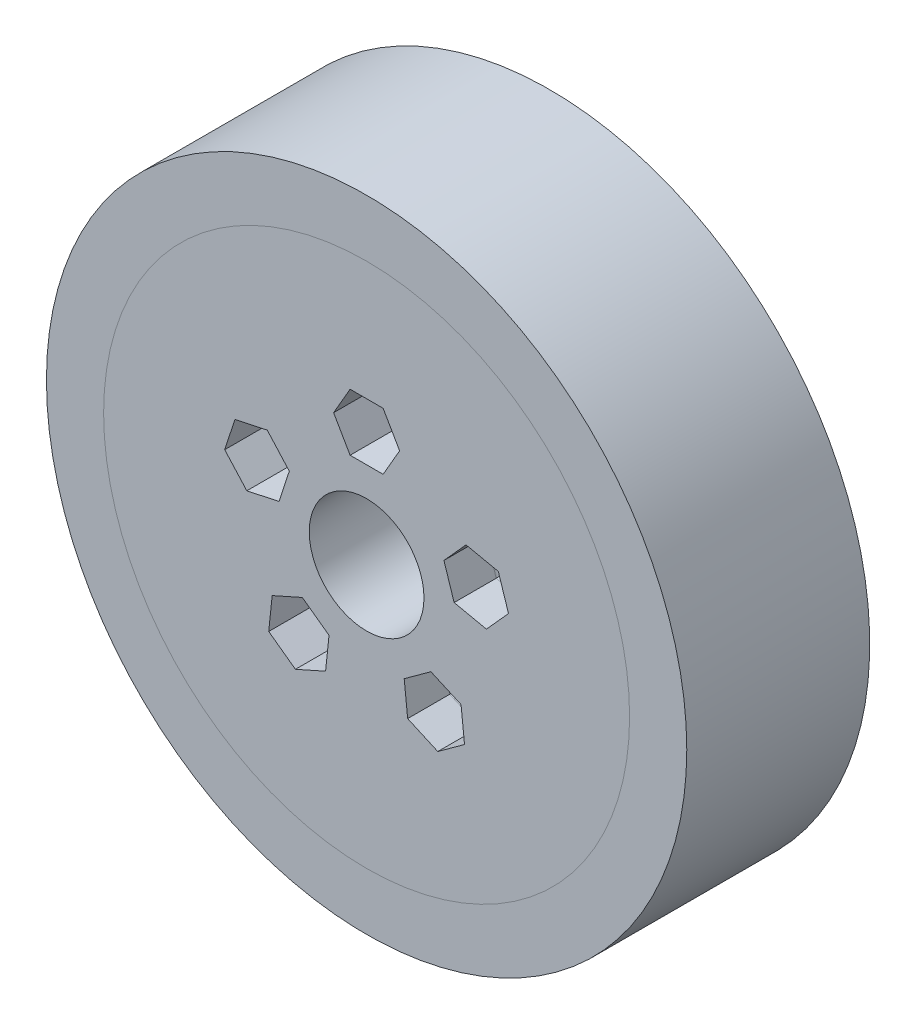
SolidWorks part; units mm, degrees
ref_plane "Front Plane" through (0, 0, 0) normal (0, 0, 1) x (1, 0, 0)
ref_plane "Top Plane" through (0, 0, 0) normal (0, 1, 0) x (1, 0, 0)
ref_plane "Right Plane" through (0, 0, 0) normal (1, 0, 0) x (0, 0, -1)
sketch "Sketch1" plane through (0, 0, 0) normal (0, 0, 1) x (1, 0, 0)
  circle A0 centre (0, 0) radius 44.45 construction
  circle A1 centre (0, 0) radius 36.5125
  circle A2 centre (0, 0) radius 7.9629
  dimension "D1" = 88.9
  dimension "D2" = 15.9258
  dimension "D3" = 7.9375
extrude "Boss-Extrude1" add sketch "Sketch1" along normal blind 25.4
sketch "Sketch3" [suppressed] plane through (0, 0, 0) normal (1, 0, 0) x (0, 0, -1)
  line L0 (-10.3109, 36.5125) -> (-7.3779, 41.5925)
  line L1 (0, 36.5125) -> (-25.4, 36.5125) construction
  line L2 (-7.3779, 41.5925) -> (-4.2029, 41.5925)
  line L3 (-4.2029, 41.5925) -> (-1.27, 36.5125)
  line L4 (0, 0) -> (0, 34.925) construction
  line L5 (0, 0) -> (16.9074, 0) construction
  line L6 (-10.3109, 36.5125) -> (-1.27, 36.5125)
  line L7 (-5.7904, 41.5925) -> (-5.7904, 36.5125) construction
  dimension "D1" = 69.85
  dimension "D2" = 5.08
  dimension "D3" = 30
  dimension "D4" = 3.175
  dimension "D5" = 1.27
revolve "Revolve1" [suppressed] add sketch "Sketch3" angle 360 about L5
sketch "Sketch4" [suppressed] plane through (0, 0, 0) normal (0, 0, 1) x (1, 0, 0)
  line L0 (0, 0) -> (-7.2225, 40.9606) construction
  line L1 (0, 0) -> (7.2225, 40.9606) construction
  line L3 (0, 41.5925) -> (0, 0) construction
  line L4 (7.3339, 41.5925) -> (-7.3339, 41.5925) construction
  line L5 (6.3403, 35.9578) -> (6.9137, 39.2096)
  line L6 (-6.9137, 39.2096) -> (-6.3403, 35.9578)
  circle A0 centre (0, 0) radius 41.5925 construction
  arc A1 (6.9137, 39.2096) -> (-6.9137, 39.2096) centre (0, 0) ccw
  arc A2 (6.3403, 35.9578) -> (-6.3403, 35.9578) centre (0, 0) ccw
  circle A4 centre (0, 0) radius 36.5125 construction
  point P11 (0, 41.5925)
  dimension "D2" = 1.778
  dimension "D1" = 20
extrude "Cut-Extrude2" [suppressed] cut sketch "Sketch4" along normal through all
fillet "Fillet1" [suppressed] radius 1.27
fillet "Fillet2" [suppressed] radius 0.762
pattern_circular "CirPattern1" [suppressed] count 14 over 360 reverse direction yes of bodies 104
split "Split1" [suppressed] bodies to split 105
pattern_linear "LPattern12" [suppressed] count 3 spacing 7.366 of bodies 110
combine bodies "Combine3" [suppressed] bodies to combine 111 114 113 112 110 117
sketch "Sketch2" plane through (0, 0, 0) normal (0, 0, 1) x (1, 0, 0)
  circle A0 centre (0, 0) radius 25.4
  circle A2 centre (0, 0) radius 7.9629 construction
  circle A3 centre (0, 0) radius 7.9629
  dimension "D1" = 50.8
extrude "Boss-Extrude3" add sketch "Sketch2" against normal blind 2.54
sketch "Sketch7" plane through (0, 0, 0) normal (0, 0, -1) x (-1, 0, 0)
  circle A0 centre (0, 0) radius 36.5125 construction
  circle A1 centre (0, 0) radius 44.45 construction
  circle A2 centre (0, 0) radius 36.5125
  circle A3 centre (0, 0) radius 44.45
extrude "Boss-Extrude2" add sketch "Sketch7" against normal up to surface (25.4 mm away) separate body up to face at (36.5125, 0, 25.4)
chamfer "Chamfer1" distance 1.27 angle 45 1 edges at (25.4, 0, -2.54)
sketch "Sketch8" plane through (0, 0, -2.54) normal (0, 0, -1) x (-1, 0, 0)
  line L54 (-3.1722, 20.1603) -> (-3.1669, 20.1266)
  line L55 (-1.56, 20.3144) -> (-1.5626, 20.3484)
  line L56 (1.5626, 20.3484) -> (1.56, 20.3144)
  line L57 (3.1669, 20.1266) -> (3.1722, 20.1603)
  line L58 (6.2131, 19.4395) -> (6.2028, 19.4071)
  line L59 (7.723, 18.8538) -> (7.7359, 18.8853)
  line L60 (10.5287, 17.4827) -> (10.5112, 17.4535)
  line L61 (11.8628, 16.5645) -> (11.8827, 16.5922)
  line L62 (14.2767, 14.5833) -> (14.2529, 14.559)
  line L63 (15.3631, 13.3822) -> (15.3888, 13.4046)
  line L64 (17.255, 10.8978) -> (17.2262, 10.8796)
  line L65 (18.0351, 9.4785) -> (18.0653, 9.4944)
  line L66 (19.3031, 6.6248) -> (19.2709, 6.6137)
  line L67 (19.7349, 5.0639) -> (19.7679, 5.0723)
  line L68 (20.3106, 1.9946) -> (20.2767, 1.9913)
  line L69 (20.3708, 0.3762) -> (20.4048, 0.3768)
  line L70 (20.2231, -2.7431) -> (20.1893, -2.7385)
  line L71 (19.9084, -4.3318) -> (19.9417, -4.339)
  line L72 (19.0454, -7.3329) -> (19.0136, -7.3207)
  line L73 (18.3728, -8.8062) -> (18.4035, -8.8209)
  line L74 (16.8409, -11.5274) -> (16.8128, -11.5082)
  line L75 (15.8467, -12.8059) -> (15.8732, -12.8273)
  line L76 (13.7286, -15.1005) -> (13.7056, -15.0753)
  line L77 (12.4663, -16.1152) -> (12.4872, -16.1422)
  line L78 (9.8761, -17.8595) -> (9.8596, -17.8297)
  line L79 (8.4139, -18.5558) -> (8.4279, -18.5868)
  line L80 (5.4912, -19.6557) -> (5.482, -19.6229)
  line L81 (3.9078, -19.996) -> (3.9143, -20.0294)
  line L82 (0.8103, -20.3922) -> (0.8089, -20.3582)
  line L83 (-0.8089, -20.3582) -> (-0.8103, -20.3922)
  line L84 (-3.9143, -20.0294) -> (-3.9078, -19.996)
  line L85 (-5.482, -19.6229) -> (-5.4912, -19.6557)
  line L86 (-8.4279, -18.5868) -> (-8.4139, -18.5558)
  line L87 (-9.8596, -17.8297) -> (-9.8761, -17.8595)
  line L88 (-12.4872, -16.1422) -> (-12.4663, -16.1152)
  line L89 (-13.7056, -15.0753) -> (-13.7286, -15.1005)
  line L90 (-15.8732, -12.8273) -> (-15.8467, -12.8059)
  line L91 (-16.8128, -11.5082) -> (-16.8409, -11.5274)
  line L92 (-18.4035, -8.8209) -> (-18.3728, -8.8062)
  line L93 (-19.0136, -7.3207) -> (-19.0454, -7.3329)
  line L94 (-19.9417, -4.339) -> (-19.9084, -4.3318)
  line L95 (-20.1893, -2.7385) -> (-20.2231, -2.7431)
  line L96 (-20.4048, 0.3768) -> (-20.3708, 0.3762)
  line L97 (-20.2767, 1.9913) -> (-20.3106, 1.9946)
  line L98 (-19.7679, 5.0723) -> (-19.7349, 5.0639)
  line L99 (-19.2709, 6.6137) -> (-19.3031, 6.6248)
  line L100 (-18.0653, 9.4944) -> (-18.0351, 9.4785)
  line L101 (-17.2262, 10.8796) -> (-17.255, 10.8978)
  line L102 (-15.3888, 13.4046) -> (-15.3631, 13.3822)
  line L103 (-14.2529, 14.559) -> (-14.2767, 14.5833)
  line L104 (-11.8827, 16.5922) -> (-11.8628, 16.5645)
  line L105 (-10.5112, 17.4535) -> (-10.5287, 17.4827)
  line L106 (-7.7359, 18.8853) -> (-7.723, 18.8538)
  line L107 (-6.2028, 19.4071) -> (-6.2131, 19.4395)
  line L108 (-3.1722, 20.1603) -> (-3.1669, 20.1266)
  line L109 (-1.56, 20.3144) -> (-1.5626, 20.3484)
  line L110 (1.5626, 20.3484) -> (1.56, 20.3144)
  line L111 (3.1669, 20.1266) -> (3.1722, 20.1603)
  line L112 (6.2131, 19.4395) -> (6.2028, 19.4071)
  line L113 (7.723, 18.8538) -> (7.7359, 18.8853)
  line L114 (10.5287, 17.4827) -> (10.5112, 17.4535)
  line L115 (11.8628, 16.5645) -> (11.8827, 16.5922)
  line L116 (14.2767, 14.5833) -> (14.2529, 14.559)
  line L117 (15.3631, 13.3822) -> (15.3888, 13.4046)
  line L118 (17.255, 10.8978) -> (17.2262, 10.8796)
  line L119 (18.0351, 9.4785) -> (18.0653, 9.4944)
  line L120 (19.3031, 6.6248) -> (19.2709, 6.6137)
  line L121 (19.7349, 5.0639) -> (19.7679, 5.0723)
  line L122 (20.3106, 1.9946) -> (20.2767, 1.9913)
  line L123 (20.3708, 0.3762) -> (20.4048, 0.3768)
  line L124 (20.2231, -2.7431) -> (20.1893, -2.7385)
  line L125 (19.9084, -4.3318) -> (19.9417, -4.339)
  line L126 (19.0454, -7.3329) -> (19.0136, -7.3207)
  line L127 (18.3728, -8.8062) -> (18.4035, -8.8209)
  line L128 (16.8409, -11.5274) -> (16.8128, -11.5082)
  line L129 (15.8467, -12.8059) -> (15.8732, -12.8273)
  line L130 (13.7286, -15.1005) -> (13.7056, -15.0753)
  line L131 (12.4663, -16.1152) -> (12.4872, -16.1422)
  line L132 (9.8761, -17.8595) -> (9.8596, -17.8297)
  line L133 (8.4139, -18.5558) -> (8.4279, -18.5868)
  line L134 (5.4912, -19.6557) -> (5.482, -19.6229)
  line L135 (3.9078, -19.996) -> (3.9143, -20.0294)
  line L136 (0.8103, -20.3922) -> (0.8089, -20.3582)
  line L137 (-0.8089, -20.3582) -> (-0.8103, -20.3922)
  line L138 (-3.9143, -20.0294) -> (-3.9078, -19.996)
  line L139 (-5.482, -19.6229) -> (-5.4912, -19.6557)
  line L140 (-8.4279, -18.5868) -> (-8.4139, -18.5558)
  line L141 (-9.8596, -17.8297) -> (-9.8761, -17.8595)
  line L142 (-12.4872, -16.1422) -> (-12.4663, -16.1152)
  line L143 (-13.7056, -15.0753) -> (-13.7286, -15.1005)
  line L144 (-15.8732, -12.8273) -> (-15.8467, -12.8059)
  line L145 (-16.8128, -11.5082) -> (-16.8409, -11.5274)
  line L146 (-18.4035, -8.8209) -> (-18.3728, -8.8062)
  line L147 (-19.0136, -7.3207) -> (-19.0454, -7.3329)
  line L148 (-19.9417, -4.339) -> (-19.9084, -4.3318)
  line L149 (-20.1893, -2.7385) -> (-20.2231, -2.7431)
  line L150 (-20.4048, 0.3768) -> (-20.3708, 0.3762)
  line L151 (-20.2767, 1.9913) -> (-20.3106, 1.9946)
  line L152 (-19.7679, 5.0723) -> (-19.7349, 5.0639)
  line L153 (-19.2709, 6.6137) -> (-19.3031, 6.6248)
  line L154 (-18.0653, 9.4944) -> (-18.0351, 9.4785)
  line L155 (-17.2262, 10.8796) -> (-17.255, 10.8978)
  line L156 (-15.3888, 13.4046) -> (-15.3631, 13.3822)
  line L157 (-14.2529, 14.559) -> (-14.2767, 14.5833)
  line L158 (-11.8827, 16.5922) -> (-11.8628, 16.5645)
  line L159 (-10.5112, 17.4535) -> (-10.5287, 17.4827)
  line L160 (-7.7359, 18.8853) -> (-7.723, 18.8538)
  line L161 (-6.2028, 19.4071) -> (-6.2131, 19.4395)
  arc A108 (-2.7438, 20.7336) -> (-3.1722, 20.1603) centre (-2.6782, 20.238) ccw
  arc A109 (-2.1116, 20.8075) -> (-2.7438, 20.7336) centre (0, 0) ccw
  arc A110 (-1.5626, 20.3484) -> (-2.1116, 20.8075) centre (-2.0611, 20.3101) ccw
  arc A111 (-1.56, 20.3144) -> (1.56, 20.3144) centre (0, 20.3144) ccw
  arc A112 (2.1116, 20.8075) -> (1.5626, 20.3484) centre (2.0611, 20.3101) ccw
  arc A113 (2.7438, 20.7336) -> (2.1116, 20.8075) centre (0, 0) ccw
  arc A114 (3.1722, 20.1603) -> (2.7438, 20.7336) centre (2.6782, 20.238) ccw
  arc A115 (3.1669, 20.1266) -> (6.2028, 19.4071) centre (4.6848, 19.7668) ccw
  arc A116 (6.8533, 19.7597) -> (6.2131, 19.4395) centre (6.6894, 19.2873) ccw
  arc A117 (7.4514, 19.542) -> (6.8533, 19.7597) centre (0, 0) ccw
  arc A118 (7.7359, 18.8853) -> (7.4514, 19.542) centre (7.2733, 19.0748) ccw
  arc A119 (7.723, 18.8538) -> (10.5112, 17.4535) centre (9.1171, 18.1536) ccw
  arc A120 (11.2254, 17.6466) -> (10.5287, 17.4827) centre (10.9571, 17.2247) ccw
  arc A121 (11.7572, 17.2968) -> (11.2254, 17.6466) centre (0, 0) ccw
  arc A122 (11.8827, 16.5922) -> (11.7572, 17.2968) centre (11.4762, 16.8833) ccw
  arc A123 (11.8628, 16.5645) -> (14.2529, 14.559) centre (13.0579, 15.5617) ccw
  arc A124 (14.9924, 14.5822) -> (14.2767, 14.5833) centre (14.634, 14.2336) ccw
  arc A125 (15.4292, 14.1192) -> (14.9924, 14.5822) centre (0, 0) ccw
  arc A126 (15.3888, 13.4046) -> (15.4292, 14.1192) centre (15.0604, 13.7816) ccw
  arc A127 (15.3631, 13.3822) -> (17.2262, 10.8796) centre (16.2947, 12.1309) ccw
  arc A128 (17.9512, 10.7316) -> (17.255, 10.8978) centre (17.522, 10.4751) ccw
  arc A129 (18.2695, 10.1804) -> (17.9512, 10.7316) centre (0, 0) ccw
  arc A130 (18.0653, 9.4944) -> (18.2695, 10.1804) centre (17.8327, 9.937) ccw
  arc A131 (18.0351, 9.4785) -> (19.2709, 6.6137) centre (18.653, 8.0461) ccw
  arc A132 (19.9422, 6.3025) -> (19.3031, 6.6248) centre (19.4654, 6.1518) ccw
  arc A133 (20.1248, 5.6927) -> (19.9422, 6.3025) centre (0, 0) ccw
  arc A134 (19.7679, 5.0723) -> (20.1248, 5.6927) centre (19.6436, 5.5566) ccw
  arc A135 (19.7349, 5.0639) -> (20.2767, 1.9913) centre (20.0058, 3.5276) ccw
  arc A136 (20.8581, 1.5336) -> (20.3106, 1.9946) centre (20.3595, 1.497) ccw
  arc A137 (20.8951, 0.8982) -> (20.8581, 1.5336) centre (0, 0) ccw
  arc A138 (20.4048, 0.3768) -> (20.8951, 0.8982) centre (20.3956, 0.8767) ccw
  arc A139 (20.3708, 0.3762) -> (20.1893, -2.7385) centre (20.28, -1.1812) ccw
  arc A140 (20.6496, -3.3179) -> (20.2231, -2.7431) centre (20.1559, -3.2386) ccw
  arc A141 (20.539, -3.9448) -> (20.6496, -3.3179) centre (0, 0) ccw
  arc A142 (19.9417, -4.339) -> (20.539, -3.9448) centre (20.048, -3.8505) ccw
  arc A143 (19.9084, -4.3318) -> (19.0136, -7.3207) centre (19.461, -5.8262) ccw
  arc A144 (19.3278, -7.9906) -> (19.0454, -7.3329) centre (18.8657, -7.7996) ccw
  arc A145 (19.0757, -8.5751) -> (19.3278, -7.9906) centre (0, 0) ccw
  arc A146 (18.4035, -8.8209) -> (19.0757, -8.5751) centre (18.6196, -8.37) ccw
  arc A147 (18.3728, -8.8062) -> (16.8128, -11.5082) centre (17.5928, -10.1572) ccw
  arc A148 (16.9641, -12.2325) -> (16.8409, -11.5274) centre (16.5585, -11.94) ccw
  arc A149 (16.5839, -12.7431) -> (16.9641, -12.2325) centre (0, 0) ccw
  arc A150 (15.8732, -12.8273) -> (16.5839, -12.7431) centre (16.1875, -12.4384) ccw
  arc A151 (15.8467, -12.8059) -> (13.7056, -15.0753) centre (14.7762, -13.9406) ccw
  arc A152 (13.6858, -15.8149) -> (13.7286, -15.1005) centre (13.3586, -15.4369) ccw
  arc A153 (13.1982, -16.2241) -> (13.6858, -15.8149) centre (0, 0) ccw
  arc A154 (12.4872, -16.1422) -> (13.1982, -16.2241) centre (12.8826, -15.8362) ccw
  arc A155 (12.4663, -16.1152) -> (9.8596, -17.8297) centre (11.163, -16.9724) ccw
  arc A156 (9.6697, -18.5448) -> (9.8761, -17.8595) centre (9.4385, -18.1015) ccw
  arc A157 (9.1009, -18.8305) -> (9.6697, -18.5448) centre (0, 0) ccw
  arc A158 (8.4279, -18.5868) -> (9.1009, -18.8305) centre (8.8833, -18.3803) ccw
  arc A159 (8.4139, -18.5558) -> (5.482, -19.6229) centre (6.9479, -19.0893) ccw
  arc A160 (5.1323, -20.2749) -> (5.4912, -19.6557) centre (5.0096, -19.7902) ccw
  arc A161 (4.513, -20.4217) -> (5.1323, -20.2749) centre (0, 0) ccw
  arc A162 (3.9143, -20.0294) -> (4.513, -20.4217) centre (4.4051, -19.9335) ccw
  arc A163 (3.9078, -19.996) -> (0.8089, -20.3582) centre (2.3584, -20.1771) ccw
  arc A164 (0.3183, -20.912) -> (0.8103, -20.3922) centre (0.3107, -20.4121) ccw
  arc A165 (-0.3183, -20.912) -> (0.3183, -20.912) centre (0, 0) ccw
  arc A166 (-0.8103, -20.3922) -> (-0.3183, -20.912) centre (-0.3107, -20.4121) ccw
  arc A167 (-0.8089, -20.3582) -> (-3.9078, -19.996) centre (-2.3584, -20.1771) ccw
  arc A168 (-4.513, -20.4217) -> (-3.9143, -20.0294) centre (-4.4051, -19.9335) ccw
  arc A169 (-5.1323, -20.2749) -> (-4.513, -20.4217) centre (0, 0) ccw
  arc A170 (-5.4912, -19.6557) -> (-5.1323, -20.2749) centre (-5.0096, -19.7902) ccw
  arc A171 (-5.482, -19.6229) -> (-8.4139, -18.5558) centre (-6.9479, -19.0893) ccw
  arc A172 (-9.1009, -18.8305) -> (-8.4279, -18.5868) centre (-8.8833, -18.3803) ccw
  arc A173 (-9.6697, -18.5448) -> (-9.1009, -18.8305) centre (0, 0) ccw
  arc A174 (-9.8761, -17.8595) -> (-9.6697, -18.5448) centre (-9.4385, -18.1015) ccw
  arc A175 (-9.8596, -17.8297) -> (-12.4663, -16.1152) centre (-11.163, -16.9724) ccw
  arc A176 (-13.1982, -16.2241) -> (-12.4872, -16.1422) centre (-12.8826, -15.8362) ccw
  arc A177 (-13.6858, -15.8149) -> (-13.1982, -16.2241) centre (0, 0) ccw
  arc A178 (-13.7286, -15.1005) -> (-13.6858, -15.8149) centre (-13.3586, -15.4369) ccw
  arc A179 (-13.7056, -15.0753) -> (-15.8467, -12.8059) centre (-14.7762, -13.9406) ccw
  arc A180 (-16.5839, -12.7431) -> (-15.8732, -12.8273) centre (-16.1875, -12.4384) ccw
  arc A181 (-16.9641, -12.2325) -> (-16.5839, -12.7431) centre (0, 0) ccw
  arc A182 (-16.8409, -11.5274) -> (-16.9641, -12.2325) centre (-16.5585, -11.94) ccw
  arc A183 (-16.8128, -11.5082) -> (-18.3728, -8.8062) centre (-17.5928, -10.1572) ccw
  arc A184 (-19.0757, -8.5751) -> (-18.4035, -8.8209) centre (-18.6196, -8.37) ccw
  arc A185 (-19.3278, -7.9906) -> (-19.0757, -8.5751) centre (0, 0) ccw
  arc A186 (-19.0454, -7.3329) -> (-19.3278, -7.9906) centre (-18.8657, -7.7996) ccw
  arc A187 (-19.0136, -7.3207) -> (-19.9084, -4.3318) centre (-19.461, -5.8262) ccw
  arc A188 (-20.539, -3.9448) -> (-19.9417, -4.339) centre (-20.048, -3.8505) ccw
  arc A189 (-20.6496, -3.3179) -> (-20.539, -3.9448) centre (0, 0) ccw
  arc A190 (-20.2231, -2.7431) -> (-20.6496, -3.3179) centre (-20.1559, -3.2386) ccw
  arc A191 (-20.1893, -2.7385) -> (-20.3708, 0.3762) centre (-20.28, -1.1812) ccw
  arc A192 (-20.8951, 0.8982) -> (-20.4048, 0.3768) centre (-20.3956, 0.8767) ccw
  arc A193 (-20.8581, 1.5336) -> (-20.8951, 0.8982) centre (0, 0) ccw
  arc A194 (-20.3106, 1.9946) -> (-20.8581, 1.5336) centre (-20.3595, 1.497) ccw
  arc A195 (-20.2767, 1.9913) -> (-19.7349, 5.0639) centre (-20.0058, 3.5276) ccw
  arc A196 (-20.1248, 5.6927) -> (-19.7679, 5.0723) centre (-19.6436, 5.5566) ccw
  arc A197 (-19.9422, 6.3025) -> (-20.1248, 5.6927) centre (0, 0) ccw
  arc A198 (-19.3031, 6.6248) -> (-19.9422, 6.3025) centre (-19.4654, 6.1518) ccw
  arc A199 (-19.2709, 6.6137) -> (-18.0351, 9.4785) centre (-18.653, 8.0461) ccw
  arc A200 (-18.2695, 10.1804) -> (-18.0653, 9.4944) centre (-17.8327, 9.937) ccw
  arc A201 (-17.9512, 10.7316) -> (-18.2695, 10.1804) centre (0, 0) ccw
  arc A202 (-17.255, 10.8978) -> (-17.9512, 10.7316) centre (-17.522, 10.4751) ccw
  arc A203 (-17.2262, 10.8796) -> (-15.3631, 13.3822) centre (-16.2947, 12.1309) ccw
  arc A204 (-15.4292, 14.1192) -> (-15.3888, 13.4046) centre (-15.0604, 13.7816) ccw
  arc A205 (-14.9924, 14.5822) -> (-15.4292, 14.1192) centre (0, 0) ccw
  arc A206 (-14.2767, 14.5833) -> (-14.9924, 14.5822) centre (-14.634, 14.2336) ccw
  arc A207 (-14.2529, 14.559) -> (-11.8628, 16.5645) centre (-13.0579, 15.5617) ccw
  arc A208 (-11.7572, 17.2968) -> (-11.8827, 16.5922) centre (-11.4762, 16.8833) ccw
  arc A209 (-11.2254, 17.6466) -> (-11.7572, 17.2968) centre (0, 0) ccw
  arc A210 (-10.5287, 17.4827) -> (-11.2254, 17.6466) centre (-10.9571, 17.2247) ccw
  arc A211 (-10.5112, 17.4535) -> (-7.723, 18.8538) centre (-9.1171, 18.1536) ccw
  arc A212 (-7.4514, 19.542) -> (-7.7359, 18.8853) centre (-7.2733, 19.0748) ccw
  arc A213 (-6.8533, 19.7597) -> (-7.4514, 19.542) centre (0, 0) ccw
  arc A214 (-6.2131, 19.4395) -> (-6.8533, 19.7597) centre (-6.6894, 19.2873) ccw
  arc A215 (-6.2028, 19.4071) -> (-3.1669, 20.1266) centre (-4.6848, 19.7668) ccw
  arc A216 (-2.7438, 20.7336) -> (-3.1722, 20.1603) centre (-2.6782, 20.238) ccw
  arc A217 (-2.1116, 20.8075) -> (-2.7438, 20.7336) centre (0, 0) ccw
  arc A218 (-1.5626, 20.3484) -> (-2.1116, 20.8075) centre (-2.0611, 20.3101) ccw
  arc A219 (-1.56, 20.3144) -> (1.56, 20.3144) centre (0, 20.3144) ccw
  arc A220 (2.1116, 20.8075) -> (1.5626, 20.3484) centre (2.0611, 20.3101) ccw
  arc A221 (2.7438, 20.7336) -> (2.1116, 20.8075) centre (0, 0) ccw
  arc A222 (3.1722, 20.1603) -> (2.7438, 20.7336) centre (2.6782, 20.238) ccw
  arc A223 (3.1669, 20.1266) -> (6.2028, 19.4071) centre (4.6848, 19.7668) ccw
  arc A224 (6.8533, 19.7597) -> (6.2131, 19.4395) centre (6.6894, 19.2873) ccw
  arc A225 (7.4514, 19.542) -> (6.8533, 19.7597) centre (0, 0) ccw
  arc A226 (7.7359, 18.8853) -> (7.4514, 19.542) centre (7.2733, 19.0748) ccw
  arc A227 (7.723, 18.8538) -> (10.5112, 17.4535) centre (9.1171, 18.1536) ccw
  arc A228 (11.2254, 17.6466) -> (10.5287, 17.4827) centre (10.9571, 17.2247) ccw
  arc A229 (11.7572, 17.2968) -> (11.2254, 17.6466) centre (0, 0) ccw
  arc A230 (11.8827, 16.5922) -> (11.7572, 17.2968) centre (11.4762, 16.8833) ccw
  arc A231 (11.8628, 16.5645) -> (14.2529, 14.559) centre (13.0579, 15.5617) ccw
  arc A232 (14.9924, 14.5822) -> (14.2767, 14.5833) centre (14.634, 14.2336) ccw
  arc A233 (15.4292, 14.1192) -> (14.9924, 14.5822) centre (0, 0) ccw
  arc A234 (15.3888, 13.4046) -> (15.4292, 14.1192) centre (15.0604, 13.7816) ccw
  arc A235 (15.3631, 13.3822) -> (17.2262, 10.8796) centre (16.2947, 12.1309) ccw
  arc A236 (17.9512, 10.7316) -> (17.255, 10.8978) centre (17.522, 10.4751) ccw
  arc A237 (18.2695, 10.1804) -> (17.9512, 10.7316) centre (0, 0) ccw
  arc A238 (18.0653, 9.4944) -> (18.2695, 10.1804) centre (17.8327, 9.937) ccw
  arc A239 (18.0351, 9.4785) -> (19.2709, 6.6137) centre (18.653, 8.0461) ccw
  arc A240 (19.9422, 6.3025) -> (19.3031, 6.6248) centre (19.4654, 6.1518) ccw
  arc A241 (20.1248, 5.6927) -> (19.9422, 6.3025) centre (0, 0) ccw
  arc A242 (19.7679, 5.0723) -> (20.1248, 5.6927) centre (19.6436, 5.5566) ccw
  arc A243 (19.7349, 5.0639) -> (20.2767, 1.9913) centre (20.0058, 3.5276) ccw
  arc A244 (20.8581, 1.5336) -> (20.3106, 1.9946) centre (20.3595, 1.497) ccw
  arc A245 (20.8951, 0.8982) -> (20.8581, 1.5336) centre (0, 0) ccw
  arc A246 (20.4048, 0.3768) -> (20.8951, 0.8982) centre (20.3956, 0.8767) ccw
  arc A247 (20.3708, 0.3762) -> (20.1893, -2.7385) centre (20.28, -1.1812) ccw
  arc A248 (20.6496, -3.3179) -> (20.2231, -2.7431) centre (20.1559, -3.2386) ccw
  arc A249 (20.539, -3.9448) -> (20.6496, -3.3179) centre (0, 0) ccw
  arc A250 (19.9417, -4.339) -> (20.539, -3.9448) centre (20.048, -3.8505) ccw
  arc A251 (19.9084, -4.3318) -> (19.0136, -7.3207) centre (19.461, -5.8262) ccw
  arc A252 (19.3278, -7.9906) -> (19.0454, -7.3329) centre (18.8657, -7.7996) ccw
  arc A253 (19.0757, -8.5751) -> (19.3278, -7.9906) centre (0, 0) ccw
  arc A254 (18.4035, -8.8209) -> (19.0757, -8.5751) centre (18.6196, -8.37) ccw
  arc A255 (18.3728, -8.8062) -> (16.8128, -11.5082) centre (17.5928, -10.1572) ccw
  arc A256 (16.9641, -12.2325) -> (16.8409, -11.5274) centre (16.5585, -11.94) ccw
  arc A257 (16.5839, -12.7431) -> (16.9641, -12.2325) centre (0, 0) ccw
  arc A258 (15.8732, -12.8273) -> (16.5839, -12.7431) centre (16.1875, -12.4384) ccw
  arc A259 (15.8467, -12.8059) -> (13.7056, -15.0753) centre (14.7762, -13.9406) ccw
  arc A260 (13.6858, -15.8149) -> (13.7286, -15.1005) centre (13.3586, -15.4369) ccw
  arc A261 (13.1982, -16.2241) -> (13.6858, -15.8149) centre (0, 0) ccw
  arc A262 (12.4872, -16.1422) -> (13.1982, -16.2241) centre (12.8826, -15.8362) ccw
  arc A263 (12.4663, -16.1152) -> (9.8596, -17.8297) centre (11.163, -16.9724) ccw
  arc A264 (9.6697, -18.5448) -> (9.8761, -17.8595) centre (9.4385, -18.1015) ccw
  arc A265 (9.1009, -18.8305) -> (9.6697, -18.5448) centre (0, 0) ccw
  arc A266 (8.4279, -18.5868) -> (9.1009, -18.8305) centre (8.8833, -18.3803) ccw
  arc A267 (8.4139, -18.5558) -> (5.482, -19.6229) centre (6.9479, -19.0893) ccw
  arc A268 (5.1323, -20.2749) -> (5.4912, -19.6557) centre (5.0096, -19.7902) ccw
  arc A269 (4.513, -20.4217) -> (5.1323, -20.2749) centre (0, 0) ccw
  arc A270 (3.9143, -20.0294) -> (4.513, -20.4217) centre (4.4051, -19.9335) ccw
  arc A271 (3.9078, -19.996) -> (0.8089, -20.3582) centre (2.3584, -20.1771) ccw
  arc A272 (0.3183, -20.912) -> (0.8103, -20.3922) centre (0.3107, -20.4121) ccw
  arc A273 (-0.3183, -20.912) -> (0.3183, -20.912) centre (0, 0) ccw
  arc A274 (-0.8103, -20.3922) -> (-0.3183, -20.912) centre (-0.3107, -20.4121) ccw
  arc A275 (-0.8089, -20.3582) -> (-3.9078, -19.996) centre (-2.3584, -20.1771) ccw
  arc A276 (-4.513, -20.4217) -> (-3.9143, -20.0294) centre (-4.4051, -19.9335) ccw
  arc A277 (-5.1323, -20.2749) -> (-4.513, -20.4217) centre (0, 0) ccw
  arc A278 (-5.4912, -19.6557) -> (-5.1323, -20.2749) centre (-5.0096, -19.7902) ccw
  arc A279 (-5.482, -19.6229) -> (-8.4139, -18.5558) centre (-6.9479, -19.0893) ccw
  arc A280 (-9.1009, -18.8305) -> (-8.4279, -18.5868) centre (-8.8833, -18.3803) ccw
  arc A281 (-9.6697, -18.5448) -> (-9.1009, -18.8305) centre (0, 0) ccw
  arc A282 (-9.8761, -17.8595) -> (-9.6697, -18.5448) centre (-9.4385, -18.1015) ccw
  arc A283 (-9.8596, -17.8297) -> (-12.4663, -16.1152) centre (-11.163, -16.9724) ccw
  arc A284 (-13.1982, -16.2241) -> (-12.4872, -16.1422) centre (-12.8826, -15.8362) ccw
  arc A285 (-13.6858, -15.8149) -> (-13.1982, -16.2241) centre (0, 0) ccw
  arc A286 (-13.7286, -15.1005) -> (-13.6858, -15.8149) centre (-13.3586, -15.4369) ccw
  arc A287 (-13.7056, -15.0753) -> (-15.8467, -12.8059) centre (-14.7762, -13.9406) ccw
  arc A288 (-16.5839, -12.7431) -> (-15.8732, -12.8273) centre (-16.1875, -12.4384) ccw
  arc A289 (-16.9641, -12.2325) -> (-16.5839, -12.7431) centre (0, 0) ccw
  arc A290 (-16.8409, -11.5274) -> (-16.9641, -12.2325) centre (-16.5585, -11.94) ccw
  arc A291 (-16.8128, -11.5082) -> (-18.3728, -8.8062) centre (-17.5928, -10.1572) ccw
  arc A292 (-19.0757, -8.5751) -> (-18.4035, -8.8209) centre (-18.6196, -8.37) ccw
  arc A293 (-19.3278, -7.9906) -> (-19.0757, -8.5751) centre (0, 0) ccw
  arc A294 (-19.0454, -7.3329) -> (-19.3278, -7.9906) centre (-18.8657, -7.7996) ccw
  arc A295 (-19.0136, -7.3207) -> (-19.9084, -4.3318) centre (-19.461, -5.8262) ccw
  arc A296 (-20.539, -3.9448) -> (-19.9417, -4.339) centre (-20.048, -3.8505) ccw
  arc A297 (-20.6496, -3.3179) -> (-20.539, -3.9448) centre (0, 0) ccw
  arc A298 (-20.2231, -2.7431) -> (-20.6496, -3.3179) centre (-20.1559, -3.2386) ccw
  arc A299 (-20.1893, -2.7385) -> (-20.3708, 0.3762) centre (-20.28, -1.1812) ccw
  arc A300 (-20.8951, 0.8982) -> (-20.4048, 0.3768) centre (-20.3956, 0.8767) ccw
  arc A301 (-20.8581, 1.5336) -> (-20.8951, 0.8982) centre (0, 0) ccw
  arc A302 (-20.3106, 1.9946) -> (-20.8581, 1.5336) centre (-20.3595, 1.497) ccw
  arc A303 (-20.2767, 1.9913) -> (-19.7349, 5.0639) centre (-20.0058, 3.5276) ccw
  arc A304 (-20.1248, 5.6927) -> (-19.7679, 5.0723) centre (-19.6436, 5.5566) ccw
  arc A305 (-19.9422, 6.3025) -> (-20.1248, 5.6927) centre (0, 0) ccw
  arc A306 (-19.3031, 6.6248) -> (-19.9422, 6.3025) centre (-19.4654, 6.1518) ccw
  arc A307 (-19.2709, 6.6137) -> (-18.0351, 9.4785) centre (-18.653, 8.0461) ccw
  arc A308 (-18.2695, 10.1804) -> (-18.0653, 9.4944) centre (-17.8327, 9.937) ccw
  arc A309 (-17.9512, 10.7316) -> (-18.2695, 10.1804) centre (0, 0) ccw
  arc A310 (-17.255, 10.8978) -> (-17.9512, 10.7316) centre (-17.522, 10.4751) ccw
  arc A311 (-17.2262, 10.8796) -> (-15.3631, 13.3822) centre (-16.2947, 12.1309) ccw
  arc A312 (-15.4292, 14.1192) -> (-15.3888, 13.4046) centre (-15.0604, 13.7816) ccw
  arc A313 (-14.9924, 14.5822) -> (-15.4292, 14.1192) centre (0, 0) ccw
  arc A314 (-14.2767, 14.5833) -> (-14.9924, 14.5822) centre (-14.634, 14.2336) ccw
  arc A315 (-14.2529, 14.559) -> (-11.8628, 16.5645) centre (-13.0579, 15.5617) ccw
  arc A316 (-11.7572, 17.2968) -> (-11.8827, 16.5922) centre (-11.4762, 16.8833) ccw
  arc A317 (-11.2254, 17.6466) -> (-11.7572, 17.2968) centre (0, 0) ccw
  arc A318 (-10.5287, 17.4827) -> (-11.2254, 17.6466) centre (-10.9571, 17.2247) ccw
  arc A319 (-10.5112, 17.4535) -> (-7.723, 18.8538) centre (-9.1171, 18.1536) ccw
  arc A320 (-7.4514, 19.542) -> (-7.7359, 18.8853) centre (-7.2733, 19.0748) ccw
  arc A321 (-6.8533, 19.7597) -> (-7.4514, 19.542) centre (0, 0) ccw
  arc A322 (-6.2131, 19.4395) -> (-6.8533, 19.7597) centre (-6.6894, 19.2873) ccw
  arc A323 (-6.2028, 19.4071) -> (-3.1669, 20.1266) centre (-4.6848, 19.7668) ccw
  dimension "D1" = 0
extrude "Cut-Extrude3" cut sketch "Sketch8" against normal blind 2.54
sketch "Sketch9" plane through (0, 0, 0) normal (0, 0, -1) x (-1, 0, 0)
  circle A0 centre (15.2169, 4.9443) radius 1.8288 construction
  circle A1 centre (9.4046, -12.9443) radius 1.8288 construction
  circle A2 centre (-9.4046, -12.9443) radius 1.8288 construction
  circle A3 centre (-15.2169, 4.9443) radius 1.8288 construction
  circle A4 centre (0, 16) radius 1.8288 construction
  circle A5 centre (15.2169, 4.9443) radius 1.8288
  circle A6 centre (9.4046, -12.9443) radius 1.8288
  circle A7 centre (-9.4046, -12.9443) radius 1.8288
  circle A8 centre (-15.2169, 4.9443) radius 1.8288
  circle A9 centre (0, 16) radius 1.8288
extrude "Cut-Extrude4" cut sketch "Sketch9" against normal through all
sketch "Sketch11" plane through (0, 0, 25.4) normal (0, 0, 1) x (1, 0, 0)
  line L1 (2.2914, 12.0312) -> (4.5827, 16)
  line L2 (4.5827, 16) -> (2.2914, 19.9688)
  line L3 (2.2914, 19.9688) -> (-2.2914, 19.9688)
  line L4 (-2.2914, 19.9688) -> (-4.5827, 16)
  line L5 (-4.5827, 16) -> (-2.2914, 12.0312)
  line L6 (-2.2914, 12.0312) -> (2.2914, 12.0312)
  circle A0 centre (0, 16) radius 3.9688 construction
  dimension "D1" = 7.9375
extrude "Cut-Extrude5" cut sketch "Sketch11" against normal blind 6.35
fillet "Fillet3" radius 0.508 7 edges at (1.8288, 16, 19.05) (-3.437, 14.0156, 19.05) (-3.437, 17.9844, 19.05) (0, 19.9688, 19.05) (3.437, 17.9844, 19.05) (3.437, 14.0156, 19.05) (0, 12.0312, 19.05)
pattern_circular "CirPattern3" count 5 over 360 about axis through (0, 0, 25.4) along (0, 0, 1) of "Fillet3", "Cut-Extrude5"
sketch "Sketch12" plane through (0, 0, 25.4) normal (0, 0, 1) x (1, 0, 0)
  line L0 (-13.8008, 9.3027) -> (-18.2833, 8.3499) construction
  line L1 (-10.7343, 5.8971) -> (-13.8008, 9.3027) construction
  line L2 (-12.1505, 1.5386) -> (-10.7343, 5.8971) construction
  line L3 (-16.633, 0.5858) -> (-12.1505, 1.5386) construction
  line L4 (-19.6995, 3.9915) -> (-16.633, 0.5858) construction
  line L5 (-13.1121, -10.2506) -> (-13.5911, -14.8082) construction
  line L6 (-8.9255, -8.3867) -> (-13.1121, -10.2506) construction
  line L7 (-5.218, -11.0803) -> (-8.9255, -8.3867) construction
  line L8 (-5.6971, -15.6379) -> (-5.218, -11.0803) construction
  line L9 (-9.8836, -17.5019) -> (-5.6971, -15.6379) construction
  line L10 (5.6971, -15.6379) -> (9.8836, -17.5019) construction
  line L11 (5.218, -11.0803) -> (5.6971, -15.6379) construction
  line L12 (8.9255, -8.3867) -> (5.218, -11.0803) construction
  line L13 (13.5911, -14.8082) -> (13.1121, -10.2506) construction
  line L14 (13.1121, -10.2506) -> (8.9255, -8.3867) construction
  line L15 (16.633, 0.5858) -> (19.6995, 3.9915) construction
  line L16 (12.1505, 1.5386) -> (16.633, 0.5858) construction
  line L17 (10.7343, 5.8971) -> (12.1505, 1.5386) construction
  line L18 (13.8008, 9.3027) -> (10.7343, 5.8971) construction
  line L19 (18.2833, 8.3499) -> (13.8008, 9.3027) construction
  line L20 (4.5827, 16) -> (2.2914, 19.9688) construction
  line L21 (2.2914, 12.0312) -> (4.5827, 16) construction
  line L22 (-2.2914, 12.0312) -> (2.2914, 12.0312) construction
  line L23 (-4.5827, 16) -> (-2.2914, 12.0312) construction
  line L24 (-2.2914, 19.9688) -> (-4.5827, 16) construction
  line L25 (-13.8008, 9.3027) -> (-14.9262, 9.0635)
  line L26 (-10.7343, 5.8971) -> (-13.8008, 9.3027)
  line L27 (-12.1505, 1.5386) -> (-10.7343, 5.8971)
  line L28 (-16.633, 0.5858) -> (-12.1505, 1.5386)
  line L29 (-17.4029, 1.4409) -> (-16.633, 0.5858)
  line L30 (-13.1121, -10.2506) -> (-13.2323, -11.3949)
  line L31 (-8.9255, -8.3867) -> (-13.1121, -10.2506)
  line L32 (-5.218, -11.0803) -> (-8.9255, -8.3867)
  line L33 (-5.6971, -15.6379) -> (-5.218, -11.0803)
  line L34 (-6.7482, -16.1059) -> (-5.6971, -15.6379)
  line L35 (5.6971, -15.6379) -> (6.7482, -16.1059)
  line L36 (5.218, -11.0803) -> (5.6971, -15.6379)
  line L37 (8.9255, -8.3867) -> (5.218, -11.0803)
  line L38 (13.2323, -11.3949) -> (13.1121, -10.2506)
  line L39 (13.1121, -10.2506) -> (8.9255, -8.3867)
  line L40 (16.633, 0.5858) -> (17.4029, 1.4409)
  line L41 (12.1505, 1.5386) -> (16.633, 0.5858)
  line L42 (10.7343, 5.8971) -> (12.1505, 1.5386)
  line L43 (13.8008, 9.3027) -> (10.7343, 5.8971)
  line L44 (14.9262, 9.0635) -> (13.8008, 9.3027)
  line L45 (4.5827, 16) -> (4.0074, 16.9965)
  line L46 (2.2914, 12.0312) -> (4.5827, 16)
  line L47 (-2.2914, 12.0312) -> (2.2914, 12.0312)
  line L48 (-4.5827, 16) -> (-2.2914, 12.0312)
  line L49 (-4.0074, 16.9965) -> (-4.5827, 16)
  arc A0 (-17.4029, 1.4409) -> (-13.2323, -11.3949) centre (0, 0) ccw
  circle A1 centre (0, 0) radius 7.9629 construction
  circle A2 centre (0, 0) radius 7.9629
  arc A3 (-4.0074, 16.9965) -> (-14.9262, 9.0635) centre (0, 0) ccw
  arc A4 (14.9262, 9.0635) -> (4.0074, 16.9965) centre (0, 0) ccw
  arc A5 (13.2323, -11.3949) -> (17.4029, 1.4409) centre (0, 0) ccw
  arc A6 (-6.7482, -16.1059) -> (6.7482, -16.1059) centre (0, 0) ccw
  dimension "D1" = 34.925
extrude "Boss-Extrude4" [suppressed] add sketch "Sketch12" along normal blind 3.175
